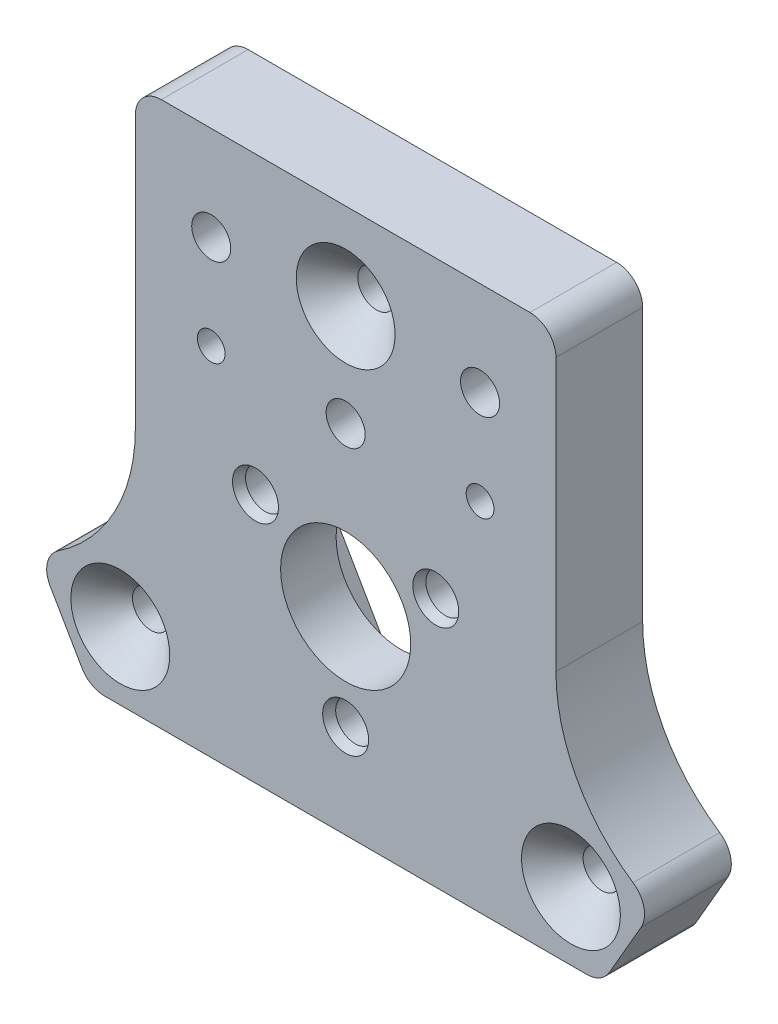
SolidWorks part; units mm, degrees
note: '?' marks a value the reader was unsure of.
other "tool plate"
material "PET"
ref_plane "Front" through (0, 0, 0) normal (0, 0, 1) x (1, 0, 0)
ref_plane "Top" through (0, 0, 0) normal (0, 1, 0) x (1, 0, 0)
ref_plane "Right" through (0, 0, 0) normal (1, 0, 0) x (0, 0, -1)
sketch "Sketch1" plane through (0, 0, 0) normal (0, 0, 1) x (1, 0, 0)
  line L0 (0, 0) -> (0, 30) construction
  line L1 (0, 0) -> (-25.9808, -15) construction
  line L2 (0, 0) -> (25.9808, -15) construction
  line L4 (-6, -1) -> (6, -1)
  line L5 (-6, -1) -> (-6, 1)
  line L6 (-6, 1) -> (6, 1)
  line L7 (6, -1) -> (6, 1)
  line L8 (-6, -1) -> (6, 1) construction
  line L9 (-6, 1) -> (6, -1) construction
  circle A0 centre (0, 0) radius 2.5
  circle A1 centre (0, 30) radius 4
  circle A2 centre (25.9808, -15) radius 4
  circle A3 centre (-25.9808, -15) radius 4
  dimension "D4" = 5
  dimension "D7" = 8
  dimension "D1" = 30
  dimension "D2" = 120
  dimension "D3" = 120
  dimension "D5" = 12
  dimension "D6" = 2
ref_plane "Plane1" through (0, 30, 0) normal (0, 1, 0) x (1, 0, 0)
sketch "Sketch10" plane through (0, 30, 0) normal (0, 1, 0) x (1, 0, 0)
  line L0 (0, 7.5) -> (0, 0) construction
  line L1 (-6, 0) -> (6, 0) construction
  circle A0 centre (0, 3.5) radius 4
  dimension "D1" = 8
  dimension "D2" = 7.5
sketch "Sketch2" plane through (0, 0, 0) normal (0, 0, 1) x (1, 0, 0)
  line L0 (0, 0) -> (0, 30) construction
  line L1 (0, 0) -> (0, 30) construction
  line L2 (-24.25, 40) -> (24.25, 40)
  line L3 (24.25, 40) -> (24.25, -5.9178)
  line L4 (-24.25, 40) -> (-24.25, -5.9178)
  line L5 (24.25, -5.9178) -> (35.5429, -12.4378)
  line L6 (35.5429, -12.4378) -> (29.5429, -22.8301)
  line L7 (29.5429, -22.8301) -> (-29.5429, -22.8301)
  line L8 (0, 0) -> (25.9808, -15) construction
  line L9 (32.0429, -18.5) -> (25.9808, -15) construction
  line L10 (-35.5429, -12.4378) -> (-29.5429, -22.8301)
  line L11 (-24.25, -5.9178) -> (-35.5429, -12.4378)
  circle A0 centre (25.9808, -15) radius 4 construction
  circle A1 centre (0, 0) radius 7.5
  point P8 (0, 40)
  point P19 (0, -22.8301)
  dimension "D3" = 7
  dimension "D5" = 15
  dimension "D1" = 24.25
  dimension "D2" = 10
  dimension "D4" = 12
  dimension "D6" = 5
extrude "Boss-Extrude1" add sketch "Sketch2" along normal blind 10
hole_wizard "CSK for M4 Flat Head Machine Screw1" positions "Sketch8" profile "Sketch9" countersink size "M4" standard "ANSI Metric"
sketch "Sketch8" plane through (0, 0, 10) normal (0, 0, 1) x (1, 0, 0)
  point P0 (-25.9808, -15)
  point P3 (0, 30)
  point P6 (25.9808, -15)
sketch "Sketch9" plane through (-25.9808, -15, 10) normal (1, 0, 0) x (0, -1, 0)
  line L0 (0, 0) -> (0, 11.2909)
  line L1 (0, 11.2909) -> (2.15, 9.999)
  line L2 (2.15, 9.999) -> (2.15, 3.55)
  line L3 (2.15, 3.55) -> (5.7, 0)
  line L5 (5.7, 0) -> (0, 0)
  line L6 (-2.15, 3.55) -> (-5.7, 0) construction
  line L10 (0, 11.2909) -> (-2.15, 9.999) construction
  line L11 (0, -6.35) -> (0, 107.95) construction
  dimension "Hole Dia." = 4.3
  dimension "Hole Depth" = 9.999
  dimension "Near C'Sink Dia." = 11.4
  dimension "Near C'Sink Angle" = 90
  dimension "Drill Angle" = 118
fillet "Fillet1" radius 20 2 edges at (-24.25, -5.9178, 5) (24.25, -5.9178, 5)
sketch "Sketch44" plane through (0, 0, 0) normal (0, 0, -1) x (-1, 0, 0)
  line L0 (10.3923, 10) -> (-10.3923, 10)
  line L1 (0, -20) -> (17.3205, 10) construction
  line L2 (17.3205, 10) -> (-17.3205, 10) construction
  line L3 (-17.3205, 10) -> (0, -20) construction
  line L4 (-13.8564, 4) -> (-3.4641, -14)
  line L5 (3.4641, -14) -> (13.8564, 4)
  line L6 (-17.3205, 10) -> (0, -20) construction
  line L7 (0, -20) -> (17.3205, 10) construction
  line L8 (17.3205, 10) -> (-17.3205, 10) construction
  circle A0 centre (0, 0) radius 10 construction
  arc A1 (-3.4641, -14) -> (3.4641, -14) centre (0, -12) ccw
  arc A2 (10.3923, 10) -> (13.8564, 4) centre (10.3923, 6) cw
  arc A3 (-10.3923, 10) -> (-13.8564, 4) centre (-10.3923, 6) ccw
  dimension "D1" = 20
  dimension "D3" = 4
  dimension "D2" = 0
extrude "v-groove cutout" cut sketch "Sketch44" against normal blind 3.6
sketch "Sketch13" plane through (0, 0, 0) normal (0, 0, -1) x (-1, 0, 0)
  circle A0 centre (-10.3923, 6) radius 2.25
  circle A1 centre (10.3923, 6) radius 2.25
  circle A2 centre (0, -12) radius 2.25
  arc A3 (-10.3923, 10) -> (-13.8564, 4) centre (-10.3923, 6) ccw construction
  arc A4 (13.8564, 4) -> (10.3923, 10) centre (10.3923, 6) ccw construction
  arc A5 (-3.4641, -14) -> (3.4641, -14) centre (0, -12) ccw construction
  dimension "D1" = 4.5
extrude "standard tapered insert cutout" cut sketch "Sketch13" against normal through all and the other way through all
chamfer "taper for inserts" distance 0.4 angle 70 3 edges at (-2.25, -12, 10) (8.1423, 6, 10) (-12.6423, 6, 10) first distance on face at (8.1423, 6, 10)
other "Move Face1" flip direction yes face at (-8.6603, -5, 1.8) face at (0, -15, 1.8) face at (8.6603, -5, 1.8) face at (12.9904, 7.5, 1.8) face at (-12.9904, 7.5, 1.8) face at (0, 10, 1.8) parameters "D1"=0.5
ref_axis "Axis2" through (0, 30, 0) along (0, 0, 1)?
ref_plane "Plane5" through (0, 30, 0) normal (0, 1, 0) x (1, 0, 0)
sketch "Sketch46" plane through (0, 30, 0) normal (0, 1, 0) x (1, 0, 0)
  line L0 (0, 0) -> (0, 0.3) construction
  line L1 (0, 5.3) -> (0, -4.7)
  line L2 (0, 7.5) -> (0, 0) construction
  circle A0 centre (0, 0.3) radius 5 construction
  arc A1 (0, -4.7) -> (0, 5.3) centre (0, 0.3) cw
  dimension "D1" = 10
  dimension "D2" = 3.2
revolve "tool ball cutout" cut sketch "Sketch46" angle 360 about L0
pattern_circular "CirPattern2" count 3 over 360 about axis through (0, 0, 0) along (0, 0, 1) of "tool ball cutout"
sketch "Sketch47" plane through (0, 0, 0) normal (0, 0, -1) x (-1, 0, 0)
  line L0 (-15.5, 49.2699) -> (-15.5, 18.2699) construction
  line L1 (-15.5, 18.2699) -> (15.5, 18.2699) construction
  circle A0 centre (-15.5, 18.2699) radius 1.6
  circle A1 centre (15.5, 18.2699) radius 1.6
  dimension "D3" = 3.2
  dimension "D4" = 3.2
  dimension "D1" = 31
  dimension "D2" = 31
extrude "Cut-Extrude1" cut sketch "Sketch47" against normal through all
sketch "Sketch48" plane through (0, 0, 0) normal (0, 0, -1) x (-1, 0, 0)
  line L0 (-15.5, 18.2699) -> (-15.5, 40) construction
  line L1 (-24.25, 40) -> (24.25, 40) construction
  line L2 (-15.5, 18.2699) -> (15.5, 18.2699) construction
  line L3 (15.5, 18.2699) -> (15.5, 40) construction
  point P5 (0, 18.2699)
  point P9 (-15.5, 29.1349)
  point P10 (15.5, 29.1349)
hole_wizard "CSK for M4 Flat Head Machine Screw2" positions "Sketch49" profile "Sketch50" countersink size "M4" standard "ANSI Metric"
sketch "Sketch49" plane through (0, 0, 0) normal (0, 0, -1) x (-1, 0, 0)
  point P0 (-15.5, 29.1349)
  point P3 (0, 18.2699)
  point P6 (15.5, 29.1349)
sketch "Sketch50" plane through (15.5, 29.1349, 0) normal (1, 0, 0) x (0, 1, 0)
  line L0 (0, 0) -> (0, 11.4519)
  line L1 (0, 11.4519) -> (2.25, 10.1)
  line L2 (2.25, 10.1) -> (2.25, 2.45)
  line L3 (2.25, 2.45) -> (4.7, 0)
  line L5 (4.7, 0) -> (0, 0)
  line L6 (-2.25, 2.45) -> (-4.7, 0) construction
  line L10 (0, 11.4519) -> (-2.25, 10.1) construction
  line L11 (0, -6.35) -> (0, 107.95) construction
  dimension "Hole Dia." = 4.5
  dimension "Hole Depth" = 10.1
  dimension "Near C'Sink Dia." = 9.4
  dimension "Near C'Sink Angle" = 90
  dimension "Drill Angle" = 118
fillet "Fillet2" radius 3 6 edges at (24.25, 40, 5) (-24.25, 40, 5) (-29.5429, -22.8301, 5) (-35.5429, -12.4378, 5) (29.5429, -22.8301, 5) (35.5429, -12.4378, 5)
